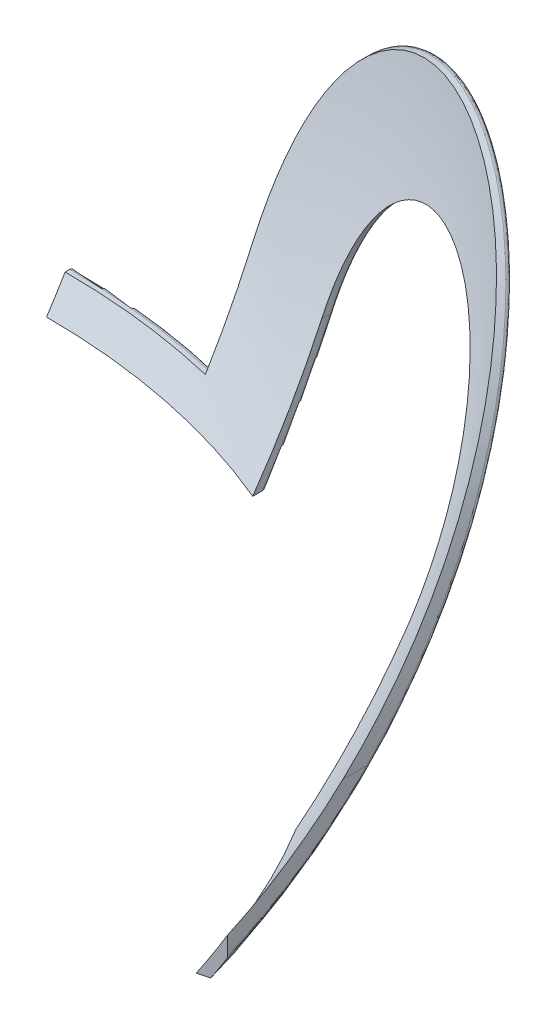
SolidWorks part; units mm, degrees
ref_plane "Front Plane" through (0, 0, 0) normal (0, 0, 1) x (1, 0, 0)
ref_plane "Top Plane" through (0, 0, 0) normal (0, 1, 0) x (1, 0, 0)
ref_plane "Right Plane" through (0, 0, 0) normal (1, 0, 0) x (0, 0, -1)
sketch "Sketch1" plane through (0, 0, 0) normal (1, 0, 0) x (0, 0, -1)
  line L0 (230.505, -11.7951) -> (234.2861, -11.7951)
  line L1 (271.7216, 121.5549) -> (274.8974, 121.5549)
  line L2 (224.3503, -11.7951) -> (230.505, -11.7951) construction
  line L4 (17.78, 127) -> (17.78, 273.6933) construction
  line L5 (0, 107.5849) -> (0, 26.3049) construction
  line L6 (0, 107.5849) -> (0, 26.3049) construction
  arc A0 (230.505, -11.7951) -> (271.7216, 121.5549) centre (17.78, 127) ccw
  arc A1 (240.6891, 5.2316) -> (254.3432, 34.513) centre (17.78, 127) ccw construction
  arc A3 (234.2861, -11.7951) -> (274.8974, 121.5549) centre (17.78, 127) ccw
  arc A4 (258.4474, 45.7893) -> (266.8095, 76.9968) centre (17.78, 127) ccw construction
  circle A5 centre (17.78, 127) radius 257.175 construction
  circle A6 centre (17.78, 127) radius 254 construction
  point P1 (0, 83.4549)
  dimension "D2" = 38.1
  dimension "D3" = 57.15
  dimension "D1" = 3.175
revolve "Revolve1" add sketch "Sketch1" angle 75 about L4 reverse direction yes
sketch "Sketch2" plane through (0, 0, 0) normal (0, 0, 1) x (1, 0, 0)
  line L10 (248.3563, 121.5549) -> (0, 121.5549)
  line L11 (0, -11.7951) -> (209.1289, -11.7951)
  line L12 (248.3563, 121.5549) -> (0, 121.5549)
  line L13 (0, -11.7951) -> (209.1289, -11.7951)
  line L16 (50.8, -2.2701) -> (-50.8, -2.2701)
  line L17 (0, -11.7951) -> (209.1289, -11.7951) construction
  line L19 (-99.06, -49.8951) -> (-99.06, 26.3049)
  line L20 (-175.26, 26.3049) -> (-175.26, -49.8951)
  line L21 (0, 121.5549) -> (0, -11.7951)
  line L22 (0, 121.5549) -> (0, -11.7951)
  line L23 (-99.06, -49.8951) -> (-99.06, 26.3049)
  line L24 (-175.26, 26.3049) -> (-175.26, -49.8951)
  line L29 (50.8, 26.3049) -> (50.8, -49.8951)
  line L30 (213.36, -49.8951) -> (213.36, 26.3049)
  line L31 (50.8, 26.3049) -> (50.8, -49.8951)
  line L32 (213.36, -49.8951) -> (213.36, 26.3049)
  line L33 (-50.8, -49.8951) -> (-50.8, 26.3049)
  line L34 (-213.36, 26.3049) -> (-213.36, -49.8951)
  line L35 (-50.8, -49.8951) -> (-50.8, 26.3049)
  line L36 (-213.36, 26.3049) -> (-213.36, -49.8951)
  line L51 (82.55, 26.3049) -> (82.55, -49.8951)
  line L52 (181.61, -49.8951) -> (181.61, 26.3049)
  arc A13 (-99.06, 26.3049) -> (-175.26, 26.3049) centre (-137.16, 26.3049) ccw
  arc A14 (-175.26, -49.8951) -> (-99.06, -49.8951) centre (-137.16, -49.8951) ccw
  arc A15 (-99.06, 26.3049) -> (-175.26, 26.3049) centre (-137.16, 26.3049) ccw
  arc A16 (-175.26, -49.8951) -> (-99.06, -49.8951) centre (-137.16, -49.8951) ccw
  arc A21 (213.36, 26.3049) -> (50.8, 26.3049) centre (132.08, 26.3049) ccw
  arc A22 (50.8, -49.8951) -> (213.36, -49.8951) centre (132.08, -49.8951) ccw
  arc A23 (213.36, 26.3049) -> (50.8, 26.3049) centre (132.08, 26.3049) ccw
  arc A24 (50.8, -49.8951) -> (213.36, -49.8951) centre (132.08, -49.8951) ccw
  arc A25 (-50.8, 26.3049) -> (-213.36, 26.3049) centre (-132.08, 26.3049) ccw
  arc A26 (-213.36, -49.8951) -> (-50.8, -49.8951) centre (-132.08, -49.8951) ccw
  arc A27 (-50.8, 26.3049) -> (-213.36, 26.3049) centre (-132.08, 26.3049) ccw
  arc A28 (-213.36, -49.8951) -> (-50.8, -49.8951) centre (-132.08, -49.8951) ccw
  arc A43 (82.55, -49.8951) -> (181.61, -49.8951) centre (132.08, -49.8951) ccw
  arc A44 (181.61, 26.3049) -> (82.55, 26.3049) centre (132.08, 26.3049) ccw
  ellipse E3 centre (0, 127) end of major axis (0, -130.175) minor radius 248.412 (209.1289, -11.7951) -> (248.3563, 121.5549) ccw
  ellipse E5 centre (0, 127) end of major axis (0, -130.175) minor radius 248.412 (209.1289, -11.7951) -> (248.3563, 121.5549) ccw
  point P16 (54.5363, 0)
  point P25 (66.7764, -2.2701)
  point P28 (0, 0)
  point P29 (0, 0)
  dimension "D3" = 9.525
  dimension "D1" = 0
  dimension "D2" = 0
  dimension "D4" = 31.75
  dimension "D5" = 0
  dimension "D6" = 0
extrude "Cut-Extrude1" cut sketch "Sketch2" against normal through all contours L52 A44 L51 L13 | L13 E5 L12 L22 L16 L31 A23 L32 region at (236.1313, 56.9557, 0) region at (132.08, 27.4989, 0)
fillet "Fillet1" radius 1.27 7 edges at (25.5697, -2.2701, -238.6293) (213.36, 8.6202, -99.0371) (120.9694, 106.822, -243.8292) (50.8, 11.7833, -242.0197) (82.55, 6.7677, -229.6023) (115.0478, 72.8143, -241.3127) (181.61, 6.0649, -153.9104)
